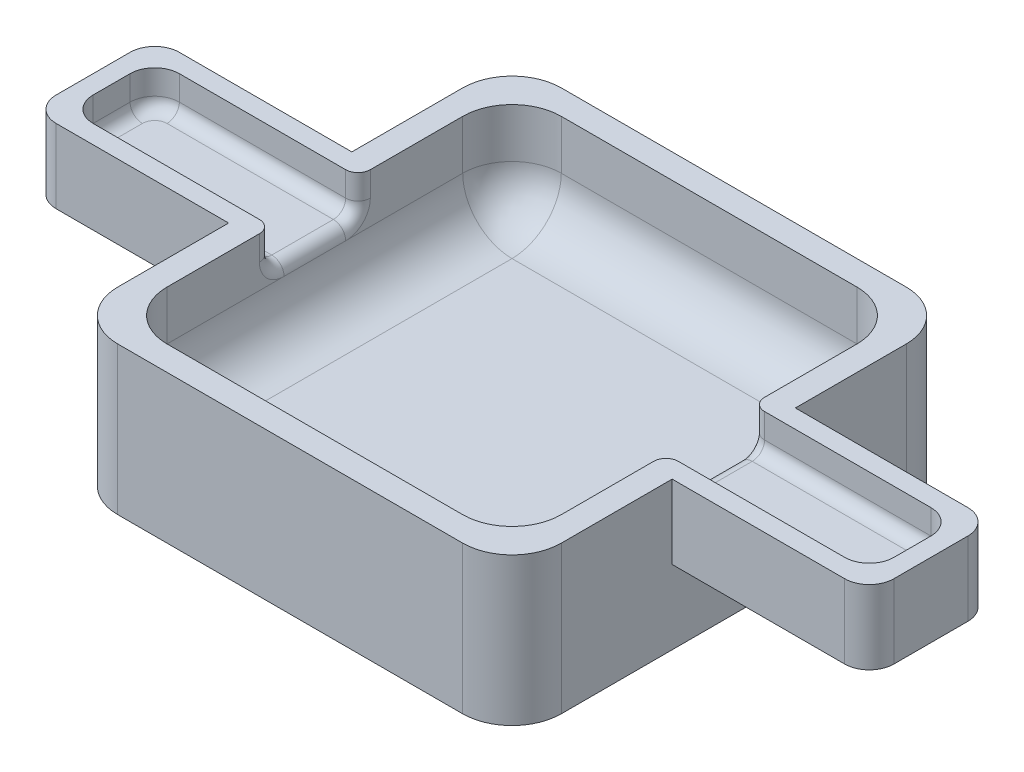
SolidWorks part; units mm, degrees
ref_plane "Front Plane" through (0, 0, 0) normal (0, 0, 1) x (1, 0, 0)
ref_plane "Top Plane" through (0, 0, 0) normal (0, 1, 0) x (1, 0, 0)
ref_plane "Right Plane" through (0, 0, 0) normal (1, 0, 0) x (0, 0, -1)
sketch "Sketch1" plane through (0, 0, 0) normal (0, 1, 0) x (1, 0, 0)
  line L1 (-7, -9) -> (7, -9)
  line L2 (-9, -7) -> (-9, 7)
  line L3 (-7, 9) -> (7, 9)
  line L4 (9, -7) -> (9, 7)
  line L5 (-9, -9) -> (9, 9) construction
  line L6 (-9, 9) -> (9, -9) construction
  arc A0 (-9, -7) -> (-7, -9) centre (-7, -7) ccw
  arc A1 (7, -9) -> (9, -7) centre (7, -7) ccw
  arc A2 (9, 7) -> (7, 9) centre (7, 7) ccw
  arc A3 (-9, 7) -> (-7, 9) centre (-7, 7) cw
  point P0 (0, 0)
  dimension "D3" = 2
  dimension "D1" = 18
  dimension "D2" = 18
extrude "Boss-Extrude1" add sketch "Sketch1" along normal blind 2
sketch "Sketch2" plane through (0, 2, 0) normal (0, 1, 0) x (1, 0, 0)
  line L0 (7, 9) -> (-7, 9) construction
  line L1 (-7, -9) -> (7, -9)
  line L2 (-9, -7) -> (-9, 7)
  line L3 (-7, 9) -> (7, 9)
  line L4 (9, -7) -> (9, 7)
  line L5 (-9, -9) -> (9, 9) construction
  line L6 (-9, 9) -> (9, -9) construction
  line L12 (-6.2212, -6.2212) -> (6.2212, 6.2212) construction
  line L13 (-6.2212, 6.2212) -> (6.2212, -6.2212) construction
  line L14 (-6, -8) -> (6, -8)
  line L15 (-8, -6) -> (-8, 6)
  line L16 (-6, 8) -> (6, 8)
  line L17 (8, -6) -> (8, 6)
  line L18 (-8, -8) -> (8, 8) construction
  line L19 (-8, 8) -> (8, -8) construction
  arc A0 (-9, -7) -> (-7, -9) centre (-7, -7) ccw
  arc A1 (7, -9) -> (9, -7) centre (7, -7) ccw
  arc A2 (9, 7) -> (7, 9) centre (7, 7) ccw
  arc A3 (-7, 9) -> (-9, 7) centre (-7, 7) ccw
  arc A4 (-8, -6) -> (-6, -8) centre (-6, -6) ccw
  arc A5 (6, -8) -> (8, -6) centre (6, -6) ccw
  arc A6 (8, 6) -> (6, 8) centre (6, 6) ccw
  arc A7 (-8, 6) -> (-6, 8) centre (-6, 6) cw
  point P0 (0, 0)
  point P20 (0, 0)
  point P25 (0, 0)
  dimension "D2" = 2
  dimension "D5" = 2
  dimension "D1" = 18
  dimension "D3" = 16
  dimension "D4" = 16
extrude "Boss-Extrude2" add sketch "Sketch2" along normal blind 4
fillet "Fillet1" radius 2 8 edges at (-7.4142, 2, 7.4142) (0, 2, 8) (7.4142, 2, 7.4142) (8, 2, 0) (7.4142, 2, -7.4142) (0, 2, -8) (-8, 2, 0) (-7.4142, 2, -7.4142)
sketch "Sketch3" plane through (0, 6, 0) normal (0, 1, 0) x (1, 0, 0)
  line L0 (-17, 0) -> (17, 0) construction
  line L1 (-9, 7) -> (-9, -7) construction
  line L2 (-9, 2.5) -> (-16, 2.5)
  line L3 (-9, 2.5) -> (-9, -2.5)
  line L4 (-9, -2.5) -> (-16, -2.5)
  line L5 (-17, 1.5) -> (-17, -1.5)
  line L6 (9, -7) -> (9, 7) construction
  line L7 (9, 2.5) -> (16, 2.5)
  line L8 (9, 2.5) -> (9, -2.5)
  line L9 (9, -2.5) -> (16, -2.5)
  line L10 (17, 1.5) -> (17, -1.5)
  arc A0 (16, -2.5) -> (17, -1.5) centre (16, -1.5) ccw
  arc A1 (17, 1.5) -> (16, 2.5) centre (16, 1.5) ccw
  arc A2 (-17, 1.5) -> (-16, 2.5) centre (-16, 1.5) cw
  arc A3 (-17, -1.5) -> (-16, -2.5) centre (-16, -1.5) ccw
  point P4 (0, 0)
  point P17 (0, 0)
  point P18 (0, 0)
  point P19 (0, 0)
  point P28 (-17, 0)
  point P29 (17, 0)
  dimension "D1" = 1
  dimension "D2" = 7
  dimension "D3" = 5
  dimension "D4" = 5
extrude "Boss-Extrude3" add sketch "Sketch3" against normal blind 3
sketch "Sketch4" plane through (0, 6, 0) normal (0, 1, 0) x (1, 0, 0)
  line L0 (-16.25, 0) -> (16.25, 0) construction
  line L9 (-8, 1.75) -> (-15.25, 1.75)
  line L10 (-8, 6) -> (-8, -6) construction
  line L11 (-8, 1.75) -> (-8, -1.75)
  line L12 (-8, -1.75) -> (-15.25, -1.75)
  line L13 (-16.25, 0.75) -> (-16.25, -0.75)
  line L14 (8, 1.75) -> (15.25, 1.75)
  line L15 (8, 1.75) -> (8, -1.75)
  line L16 (8, -1.75) -> (15.25, -1.75)
  line L17 (16.25, 0.75) -> (16.25, -0.75)
  line L18 (8, 6) -> (8, -6) construction
  line L21 (-17, 1.5) -> (-17, -1.5) construction
  arc A4 (15.25, -1.75) -> (16.25, -0.75) centre (15.25, -0.75) ccw
  arc A5 (16.25, 0.75) -> (15.25, 1.75) centre (15.25, 0.75) ccw
  arc A6 (-16.25, 0.75) -> (-15.25, 1.75) centre (-15.25, 0.75) cw
  arc A7 (-16.25, -0.75) -> (-15.25, -1.75) centre (-15.25, -0.75) ccw
  point P0 (0, 0)
  point P1 (0, 0)
  point P5 (0, 0)
  point P21 (0, 0)
  point P23 (-16.25, 0)
  point P24 (16.25, 0)
  point P25 (8, 0)
  dimension "D1" = 3.5
  dimension "D2" = 3.5
  dimension "D3" = 0.75
extrude "Cut-Extrude1" cut sketch "Sketch4" against normal blind 1.5
fillet "Fillet2" radius 0.5 16 edges at (-8, 4.5, 0) (-8, 5.25, 1.75) (-11.625, 4.5, 1.75) (-16.25, 4.5, 0) (-15.9571, 4.5, 1.4571) (-8, 5.25, -1.75) (-15.9571, 4.5, -1.4571) (-11.625, 4.5, -1.75) (8, 5.25, 1.75) (11.625, 4.5, 1.75) (15.9571, 4.5, 1.4571) (16.25, 4.5, 0) (15.9571, 4.5, -1.4571) (8, 4.5, 0) (8, 5.25, -1.75) (11.625, 4.5, -1.75)
equation "\"D2@Sketch1\"=\"D1@Sketch1\""
